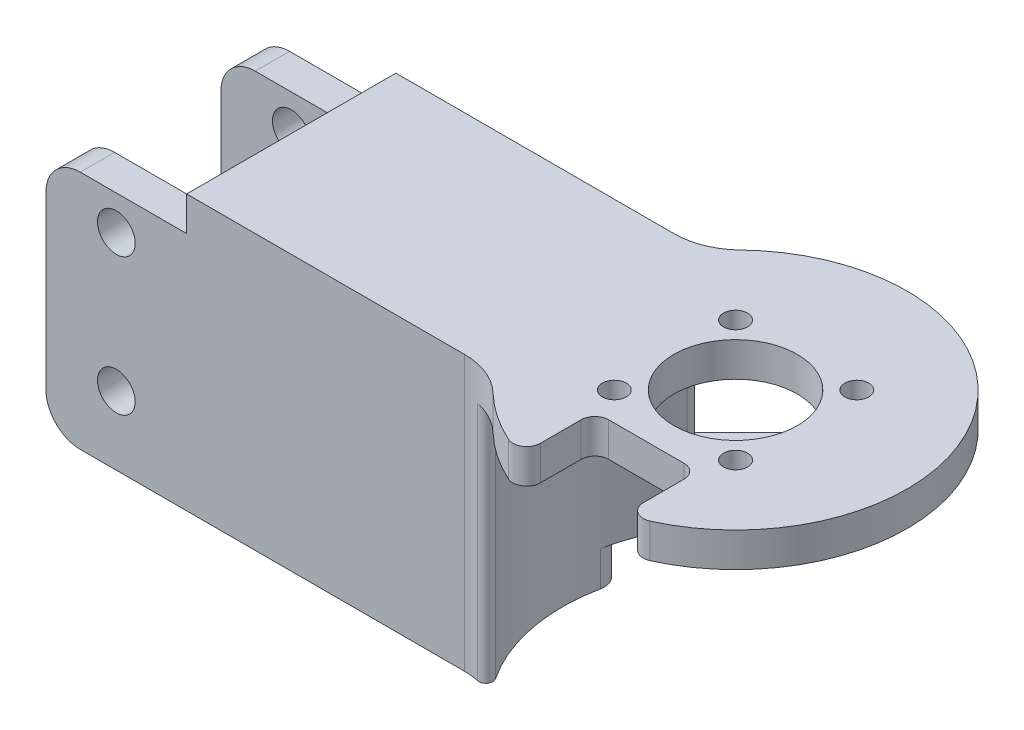
SolidWorks part; units mm, degrees
ref_plane "Front Plane" through (0, 0, 0) normal (0, 0, 1) x (1, 0, 0)
ref_plane "Top Plane" through (0, 0, 0) normal (0, 1, 0) x (1, 0, 0)
ref_plane "Right Plane" through (0, 0, 0) normal (1, 0, 0) x (0, 0, -1)
sketch "Sketch1" plane through (0, 0, 0) normal (0, 1, 0) x (1, 0, 0)
  line L0 (-8.8388, 8.8388) -> (8.8388, -8.8388) construction
  line L1 (8.8388, -8.8388) -> (-8.8388, -8.8388) construction
  line L2 (-8.8388, -8.8388) -> (8.8388, 8.8388) construction
  line L3 (8.8388, -8.8388) -> (8.8388, 8.8388) construction
  line L4 (-24.2371, 15.25) -> (-85.25, 15.25)
  line L5 (-5.5, -13) -> (5.5, -13)
  line L6 (-7.5, -15) -> (-7.5, -20.9464)
  line L8 (7.5, -15) -> (7.5, -20.9464)
  line L9 (-85.25, 15.25) -> (-85.25, 10.25)
  line L10 (-85.25, 10.25) -> (-64.75, 10.25)
  line L11 (-64.75, 10.25) -> (-64.75, -10.25)
  line L12 (-64.75, -10.25) -> (-85.25, -10.25)
  line L13 (-85.25, -10.25) -> (-85.25, -15.25)
  line L14 (-85.25, -15.25) -> (-24.2371, -15.25)
  line L15 (-64.75, 10.25) -> (-85.25, -10.25) construction
  line L16 (-75, 0) -> (0, 0) construction
  arc A0 (10.3261, -22.7678) -> (-17.3122, 18.0357) centre (0, 0) ccw
  circle A1 centre (0, 0) radius 12.5 construction
  circle A2 centre (8.8388, 8.8388) radius 1.75
  circle A3 centre (-8.8388, 8.8388) radius 1.75
  circle A4 centre (-8.8388, -8.8388) radius 1.75
  circle A5 centre (8.8388, -8.8388) radius 1.75
  circle A6 centre (0, 0) radius 9
  arc A7 (-10.3261, -22.7678) -> (-7.5, -20.9464) centre (-9.5, -20.9464) ccw
  arc A8 (10.3261, -22.7678) -> (7.5, -20.9464) centre (9.5, -20.9464) cw
  arc A9 (5.5, -13) -> (7.5, -15) centre (5.5, -15) cw
  arc A10 (-5.5, -13) -> (-7.5, -15) centre (-5.5, -15) ccw
  arc A11 (-17.3122, -18.0357) -> (-10.3261, -22.7678) centre (0, 0) ccw
  arc A12 (-24.2371, -15.25) -> (-17.3122, -18.0357) centre (-24.2371, -25.25) cw
  arc A13 (-24.2371, 15.25) -> (-17.3122, 18.0357) centre (-24.2371, 25.25) ccw
  point P36 (-19.81, -15.25)
  dimension "D1" = 25
  dimension "D2" = 50
  dimension "D3" = 3.5
  dimension "D4" = 18
  dimension "D7" = 2
  dimension "D11" = 10
  dimension "D5" = 13
  dimension "D6" = 15
  dimension "D8" = 20.5
  dimension "D9" = 75
  dimension "D10" = 5
extrude "Motor Plate" add sketch "Sketch1" along normal blind 5
sketch "Sketch3" plane through (0, 0, 0) normal (0, -1, 0) x (1, 0, 0)
  line L0 (-85.25, 15.25) -> (-85.25, 10.25)
  line L1 (-85.25, 10.25) -> (-64.75, 10.25)
  line L2 (-64.75, 10.25) -> (-64.75, -10.25)
  line L3 (-64.75, -10.25) -> (-85.25, -10.25)
  line L4 (-85.25, -10.25) -> (-85.25, -15.25)
  line L5 (-85.25, -15.25) -> (-59.75, -15.25)
  line L6 (-24.2371, -15.25) -> (-85.25, -15.25) construction
  line L7 (-59.75, -15.25) -> (-59.75, 15.25)
  line L8 (-85.25, 15.25) -> (-24.2371, 15.25) construction
  line L9 (-59.75, 15.25) -> (-85.25, 15.25)
  dimension "D1" = 5
extrude "Boss-Extrude1" add sketch "Sketch3" along normal offset from surface (35 mm away) 40 up to face at (8.8388, 5, 10.5888)
sketch "Sketch4" plane through (0, 0, 0) normal (0, -1, 0) x (1, 0, 0)
  line L0 (-59.75, -15.25) -> (-59.75, 15.25) construction
  line L1 (-24.2371, -15.25) -> (-59.75, -15.25) construction
  line L2 (-59.75, 15.25) -> (-24.2371, 15.25) construction
  line L3 (-59.75, -15.25) -> (-59.75, 15.25)
  line L4 (-24.2371, -15.25) -> (-59.75, -15.25)
  line L5 (-59.75, 15.25) -> (-24.2371, 15.25)
  arc A0 (-21.0444, 13.9534) -> (-21.0444, -13.9534) centre (0, 0) ccw
  arc A2 (-17.3122, -18.0357) -> (-24.2371, -15.25) centre (-24.2371, -25.25) ccw construction
  arc A3 (-24.2371, 15.25) -> (-17.3122, 18.0357) centre (-24.2371, 25.25) ccw construction
  arc A4 (-22.0923, -15.4827) -> (-24.2371, -15.25) centre (-24.2371, -25.25) ccw
  arc A5 (-24.2371, 15.25) -> (-22.0923, 15.4827) centre (-24.2371, 25.25) ccw
  arc A9 (-10.3261, 22.7678) -> (-17.3122, 18.0357) centre (0, 0) ccw construction
  arc A10 (-22.0923, -15.4827) -> (-21.0444, -13.9534) centre (-21.8778, -14.506) ccw
  arc A11 (-22.0923, 15.4827) -> (-21.0444, 13.9534) centre (-21.8778, 14.506) cw
  dimension "D1" = 0.25
  dimension "D2" = 1
extrude "Boss-Extrude2" add sketch "Sketch4" along normal up to surface (35 mm away) up to face at (-73.75, -35, 0)
ref_plane "Plane1" through (0, -29.8908, 0) normal (0, -1, 0) x (-1, 0, 0)
sketch "Encoder Shape" plane through (0, -29.8908, 0) normal (0, -1, 0) x (-1, 0, 0)
  line L0 (27.291, 12.4736) -> (12.4736, 27.291) construction
  line L1 (0, 0) -> (19.8823, 19.8823) construction
  line L2 (13.7937, 29.9222) -> (29.9222, 13.7937)
  line L3 (29.9222, 11.0996) -> (27.1383, 8.3157)
  line L4 (27.1383, 8.3157) -> (18.9843, 8.5672)
  line L5 (18.9843, 8.5672) -> (8.5672, 18.9843)
  line L6 (8.5672, 18.9843) -> (8.3157, 27.1383)
  line L7 (8.3157, 27.1383) -> (11.0996, 29.9222)
  line L8 (19.8823, 19.8823) -> (21.8579, 21.8579) construction
  circle A0 centre (27.291, 12.4736) radius 1.75
  circle A1 centre (12.4736, 27.291) radius 1.75
  arc A2 (29.9222, 13.7937) -> (29.9222, 11.0996) centre (28.5752, 12.4466) cw
  arc A3 (13.7937, 29.9222) -> (11.0996, 29.9222) centre (12.4466, 28.5752) ccw
  point P15 (13.7757, 13.7757)
  point P22 (12.4466, 31.2693)
  point P25 (8.8388, 8.8388)
  dimension "D1" = 20.955
  dimension "D2" = 3.5
  dimension "D9" = 1.905
  dimension "D3" = 28.1178
  dimension "D4" = 26.6192
  dimension "D5" = 2.794
  dimension "D6" = 11.43
  dimension "D7" = 14.732
  dimension "D8" = 5.842
sketch "Sketch11" plane through (0, 0, -15.25) normal (0, 0, -1) x (-1, 0, 0)
  line L0 (75, -35) -> (75, -25) construction
  line L1 (41.5994, -35) -> (85.25, -35) construction
  line L2 (24.2371, 5) -> (85.25, 5) construction
  line L3 (64.75, 5) -> (85.25, 5) construction
  line L4 (75, -25) -> (75, -5) construction
  line L5 (75, -5) -> (75, 5) construction
  circle A0 centre (75, -25) radius 2.75
  circle A1 centre (75, -5) radius 2.75
  dimension "D1" = 20
  dimension "D2" = 5.5
extrude "Cut-Extrude5" cut sketch "Sketch11" against normal through all both and the other way through all
sketch "Sketch12" plane through (0, 0, -15.25) normal (0, 0, -1) x (-1, 0, 0)
  circle A0 centre (75, -25) radius 6
  dimension "D1" = 12
extrude "Cut-Extrude6" [suppressed] cut sketch "Sketch12" along normal through all
sketch "Sketch14" plane through (0, 0, -15.25) normal (0, 0, -1) x (-1, 0, 0)
  line L0 (24.2371, 5) -> (85.25, 5) construction
  line L1 (64.75, 5) -> (85.25, 5)
  line L2 (64.75, 5) -> (64.75, 0)
  line L3 (64.75, 0) -> (85.25, 0)
  line L4 (85.25, 5) -> (85.25, 0)
  line L5 (85.25, 5) -> (85.25, -35) construction
  line L6 (64.75, 5) -> (64.75, -35) construction
  dimension "D1" = 5
extrude "Cut-Extrude7" cut sketch "Sketch14" against normal through all both and the other way through all
fillet "Fillet4" radius 5 4 edges at (-85.25, -35, 12.75) (-85.25, -35, -12.75) (-85.25, 0, 12.75) (-85.25, 0, -12.75)
sketch "Sketch24" plane through (0, -29.8908, 0) normal (0, -1, 0) x (-1, 0, 0)
  line L3 (24.2371, 15.25) -> (80.25, 15.25) construction
  line L4 (24.2371, 15.25) -> (28.8194, 15.25)
  line L6 (13.9705, 30.099) -> (30.099, 13.9705)
  line L7 (8.0625, 27.2387) -> (10.9228, 30.099)
  line L8 (8.3173, 18.9766) -> (8.0625, 27.2387)
  line L9 (13.9705, 30.099) -> (28.8194, 15.25)
  line L10 (8.0625, 27.2387) -> (10.9228, 30.099)
  line L11 (8.1657, 23.8932) -> (8.0625, 27.2387)
  arc A0 (21.0444, 13.9534) -> (8.1657, 23.8932) centre (0, 0) ccw
  arc A1 (21.0444, -13.9534) -> (21.0444, 13.9534) centre (0, 0) ccw construction
  arc A3 (22.0923, 15.4827) -> (21.0444, 13.9534) centre (21.8778, 14.506) ccw construction
  arc A4 (13.9705, 30.099) -> (10.9228, 30.099) centre (12.4466, 28.5752) ccw
  arc A5 (13.9705, 30.099) -> (10.9228, 30.099) centre (12.4466, 28.5752) ccw
  arc A6 (22.0923, 15.4827) -> (24.2371, 15.25) centre (24.2371, 25.25) ccw construction
  arc A7 (22.0923, 15.4827) -> (21.0444, 13.9534) centre (21.8778, 14.506) ccw
  arc A8 (22.0923, 15.4827) -> (24.2371, 15.25) centre (24.2371, 25.25) ccw
  dimension "D1" = 0.25
extrude "Boss-Extrude5" add sketch "Sketch24" against normal blind 7.5
sketch "Sketch26" plane through (0, -29.8908, 0) normal (0, -1, 0) x (1, 0, 0)
  line L3 (-18.9766, -8.3173) -> (-13.9705, -30.099)
  line L6 (-27.2387, -8.0625) -> (-18.9766, -8.3173)
  line L7 (-30.099, -10.9228) -> (-27.2387, -8.0625)
  line L8 (-13.9705, -30.099) -> (-30.099, -13.9705)
  line L9 (-27.2387, -8.0625) -> (-18.9766, -8.3173)
  line L10 (-30.099, -10.9228) -> (-27.2387, -8.0625)
  line L11 (-13.9705, -30.099) -> (-30.099, -13.9705)
  arc A2 (-30.099, -10.9228) -> (-30.099, -13.9705) centre (-28.5752, -12.4466) ccw
  arc A3 (-30.099, -10.9228) -> (-30.099, -13.9705) centre (-28.5752, -12.4466) ccw
  dimension "D1" = 0.25
extrude "Cut-Extrude14" cut sketch "Sketch26" along normal through all
sketch "Sketch27" plane through (0, -29.8908, 0) normal (0, -1, 0) x (1, 0, 0)
  circle A0 centre (-27.291, -12.4736) radius 2.35
  circle A1 centre (-12.4736, -27.291) radius 2.35
  dimension "D1" = 4.7
extrude "Cut-Extrude15" cut sketch "Sketch27" against normal blind 4
sketch "Sketch28" plane through (0, -29.8908, 0) normal (0, -1, 0) x (1, 0, 0)
  circle A0 centre (-27.291, -12.4736) radius 1.75
  circle A1 centre (-12.4736, -27.291) radius 1.75
  dimension "D1" = 3.5
extrude "Cut-Extrude16" cut sketch "Sketch28" against normal blind 7
fillet "Fillet5" radius 2.5 3 edges at (-8.1657, -26.1408, -23.8932) (-28.8194, -32.4454, -15.25) (-23.8932, -32.4454, -8.1657)
fillet "Fillet6" radius 10 1 edges at (-28.8194, -26.1408, -15.25)
